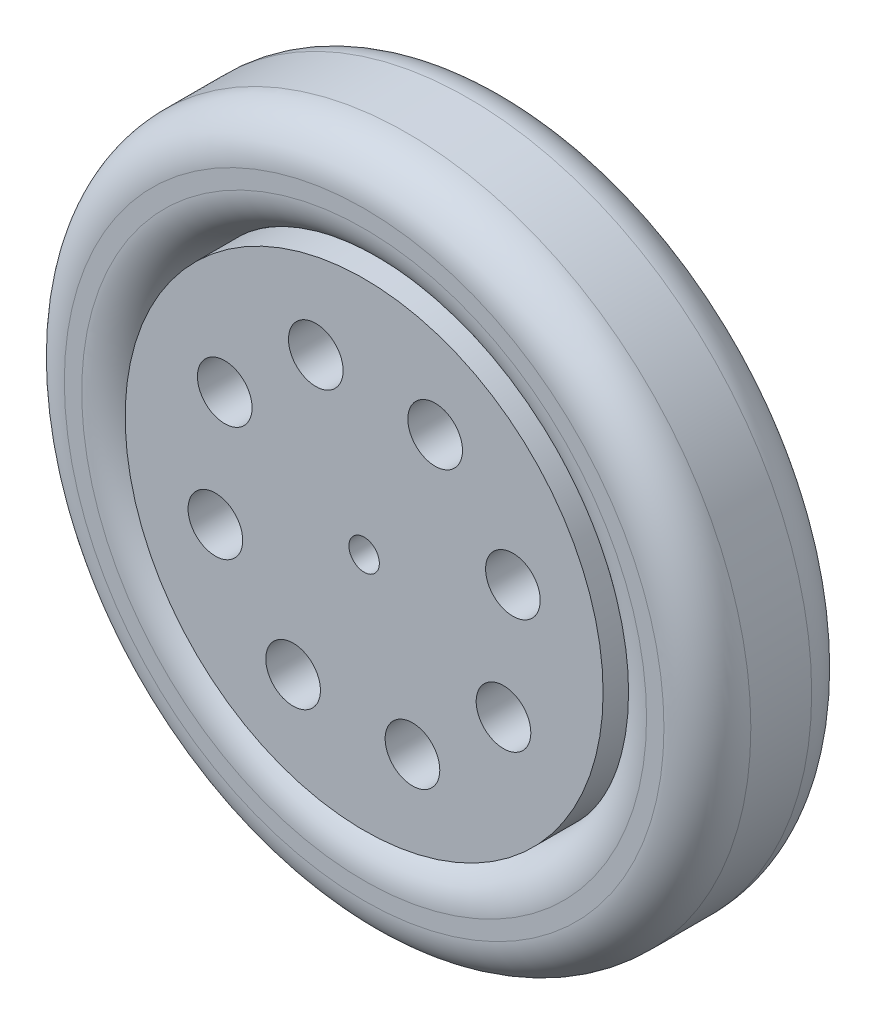
SolidWorks part; units mm, degrees
ref_plane "Front Plane" through (0, 0, 0) normal (0, 0, 1) x (1, 0, 0)
ref_plane "Top Plane" through (0, 0, 0) normal (0, 1, 0) x (1, 0, 0)
ref_plane "Right Plane" through (0, 0, 0) normal (1, 0, 0) x (0, 0, -1)
sketch "Sketch1" plane through (0, 0, 0) normal (0, 0, 1) x (1, 0, 0)
  circle A0 centre (0, 0) radius 79
  circle A1 centre (0, 0) radius 55
  dimension "D1" = 158
  dimension "D2" = 110
extrude "Boss-Extrude1" add sketch "Sketch1" along normal blind 34
fillet "Fillet1" radius 10 4 edges at (55, 0, 0) (55, 0, 34) (79, 0, 0) (79, 0, 34)
sketch "Sketch2" plane through (0, 0, 0) normal (0, 0, 1) x (1, 0, 0)
  line L0 (0, 55) -> (0, -55) construction
  line L1 (52.3081, 16.9959) -> (-52.3081, -16.9959) construction
  line L2 (32.3282, -44.4959) -> (-32.3282, 44.4959) construction
  line L3 (-32.3282, -44.4959) -> (32.3282, 44.4959) construction
  line L4 (-52.3081, 16.9959) -> (52.3081, -16.9959) construction
  line L5 (0, 0) -> (-16.9959, 52.3081) construction
  circle A0 centre (0, 0) radius 55
  circle A1 centre (-11.1246, 34.238) radius 6.2877
  circle A2 centre (16.3437, 32.0762) radius 6.2877
  circle A3 centre (34.238, 11.1246) radius 6.2877
  circle A4 centre (32.0762, -16.3437) radius 6.2877
  circle A5 centre (11.1246, -34.238) radius 6.2877
  circle A6 centre (-16.3437, -32.0762) radius 6.2877
  circle A7 centre (-34.238, -11.1246) radius 6.2877
  circle A8 centre (-32.0762, 16.3437) radius 6.2877
  circle A9 centre (0, 0) radius 3.5
  point P16 (0, 0)
  point P33 (0, 0)
  dimension "D2" = 18
  dimension "D3" = 36
  dimension "D5" = 7
  dimension "D1" = 5
  dimension "D4" = 8
extrude "Boss-Extrude2" add sketch "Sketch2" along normal blind 34
sketch "Sketch4" plane through (0, 0, 0) normal (0, 0, -1) x (-1, 0, 0)
  circle A0 centre (0, 0) radius 12.7
  dimension "D1" = 25.4
extrude "Boss-Extrude3" add sketch "Sketch4" along normal blind 2
fillet "Fillet2" radius 10 1 edges at (-12.7, 0, -2)
fillet "Fillet3" radius 5 1 edges at (55, 0, 0)
